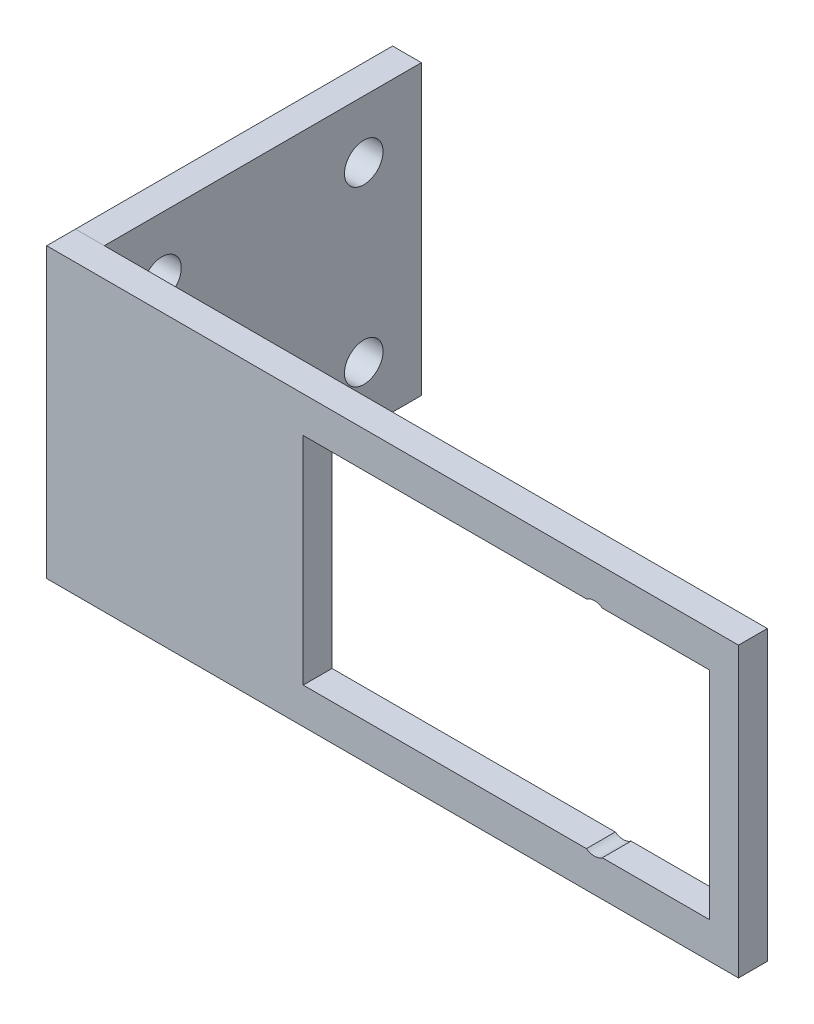
SolidWorks part; units mm, degrees
ref_plane "Front Plane" through (0, 0, 0) normal (0, 0, 1) x (1, 0, 0)
ref_plane "Top Plane" through (0, 0, 0) normal (0, 1, 0) x (1, 0, 0)
ref_plane "Right Plane" through (0, 0, 0) normal (1, 0, 0) x (0, 0, -1)
sketch "Sketch1" plane through (0, 0, 0) normal (1, 0, 0) x (0, 0, -1)
  line L0 (-31.8768, 23.0863) -> (-31.8768, -16.3439) construction
  line L2 (-44.5768, 4.0363) -> (-5.3691, 4.0363) construction
  line L4 (-45.8468, 16.7363) -> (-17.9068, 16.7363)
  line L5 (-40.7668, -3.5837) -> (-22.9868, -3.5837) construction
  line L6 (-40.7668, -3.5837) -> (-40.7668, 11.6563) construction
  line L7 (-40.7668, 11.6563) -> (-22.9868, 11.6563) construction
  line L8 (-22.9868, -3.5837) -> (-22.9868, 11.6563) construction
  line L9 (-40.7668, -3.5837) -> (-22.9868, 11.6563) construction
  line L10 (-40.7668, 11.6563) -> (-22.9868, -3.5837) construction
  line L11 (-17.9068, -8.6637) -> (-17.9068, 16.7363)
  line L12 (-45.8468, -8.6637) -> (-17.9068, -8.6637)
  line L13 (-45.8468, -8.6637) -> (-45.8468, 16.7363)
  point P17 (-31.8768, 4.0363)
  dimension "D1" = 5.08
extrude "side connecting to grip" add sketch "Sketch1" along normal blind 2.54 separate body
hole_wizard "M3 Clearance Hole1" positions "Sketch4" profile "Sketch5" hole size "M3" standard "ANSI Metric" end condition through all
sketch "Sketch4" plane through (2.54, 0, 0) normal (1, 0, 0) x (0, 0, -1)
  point P0 (-40.7668, 11.6563)
  point P3 (-22.9868, 11.6563)
  point P6 (-22.9868, -3.5837)
  point P9 (-40.7668, -3.5837)
sketch "Sketch5" plane through (2.54, 11.6563, 40.7668) normal (0, 1, 0) x (0, 0, -1)
  line L0 (0, 0) -> (0, 2.54)
  line L1 (0, 2.54) -> (1.7, 2.54)
  line L2 (1.7, 2.54) -> (1.7, 0)
  line L5 (1.7, 0) -> (0, 0)
  line L11 (0, -6.35) -> (0, 107.95) construction
  dimension "Thru Hole Dia." = 3.4
  dimension "Thru Hole Depth" = 2.54
sketch "Sketch6" plane through (2.54, 0, 0) normal (1, 0, 0) x (0, 0, -1)
  line L42 (-45.8468, 16.7363) -> (-48.3868, 16.7363)
  line L43 (-48.3868, 16.7363) -> (-48.3868, -8.6637)
  line L44 (-48.3868, -8.6637) -> (-45.8468, -8.6637)
  line L45 (-45.8468, -8.6637) -> (-45.8468, 16.7363) construction
  line L46 (-45.8468, 16.7363) -> (-45.8468, -8.6637)
  dimension "D1" = 2.54
extrude "side connecting to servo" add sketch "Sketch6" along normal blind 58.42 and the other way blind 2.54 separate body
sketch "servo holes" plane through (0, 0, 48.3868) normal (0, 0, 1) x (1, 0, 0)
  line L0 (0, 4.0363) -> (36.6866, 4.0363) construction
  circle A0 centre (48.26, 4.0363) radius 8.55 construction
  point P5 (48.26, -4.5137)
  point P8 (48.26, 12.5863)
hole_wizard "cutout servo holes" positions "Sketch8" profile "Sketch9" hole size "M2" standard "ANSI Metric" end condition through all
sketch "Sketch8" plane through (0, 0, 48.3868) normal (0, 0, 1) x (1, 0, 0)
  point P0 (48.26, 12.5863)
  point P3 (48.26, -4.5137)
sketch "Sketch9" plane through (48.26, 12.5863, 48.3868) normal (1, 0, 0) x (0, -1, 0)
  line L0 (0, 0) -> (0, 30.48)
  line L1 (0, 30.48) -> (1.2, 30.48)
  line L2 (1.2, 30.48) -> (1.2, 0)
  line L5 (1.2, 0) -> (0, 0)
  line L11 (0, -6.35) -> (0, 107.95) construction
  dimension "Thru Hole Dia." = 2.4
  dimension "Thru Hole Depth" = 30.48
sketch "Sketch10" plane through (0, 0, 48.3868) normal (0, 0, 1) x (1, 0, 0)
  line L1 (22.606, 13.5613) -> (58.42, 13.5613)
  line L2 (22.606, 13.5613) -> (22.606, -5.4887)
  line L3 (22.606, -5.4887) -> (58.42, -5.4887)
  line L4 (58.42, 13.5613) -> (58.42, -5.4887)
  line L5 (60.96, 16.7363) -> (60.96, -8.6637) construction
  line L7 (0, 4.0363) -> (36.6866, 4.0363) construction
  point P4 (22.606, 4.0363)
  dimension "D1" = 35.814
  dimension "D2" = 19.05
  dimension "D3" = 2.54
  dimension "D4" = 10.16
extrude "Cut-Extrude1" cut sketch "Sketch10" against normal blind 2.54
